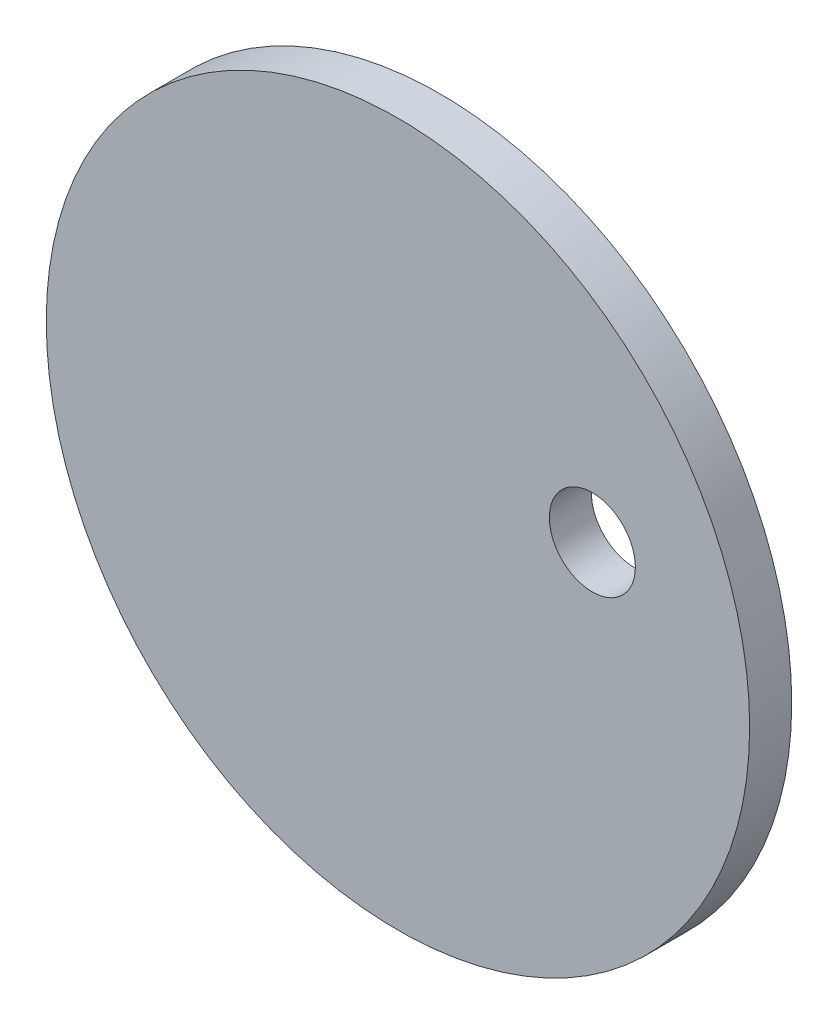
SolidWorks part; units mm, degrees
ref_plane "Front Plane" through (0, 0, 0) normal (0, 0, 1) x (1, 0, 0)
ref_plane "Top Plane" through (0, 0, 0) normal (0, 1, 0) x (1, 0, 0)
ref_plane "Right Plane" through (0, 0, 0) normal (1, 0, 0) x (0, 0, -1)
sketch "Sketch1" plane through (0, 0, 0) normal (0, 0, 1) x (1, 0, 0)
  circle A0 centre (0, 0) radius 76.4143
  circle A1 centre (42.2343, 17.7048) radius 9.3474
extrude "Extrude1" add sketch "Sketch1" against normal blind 9.144
ref_axis "Axis1" through (0, 0, -9.144) along (0, 0, 1)
